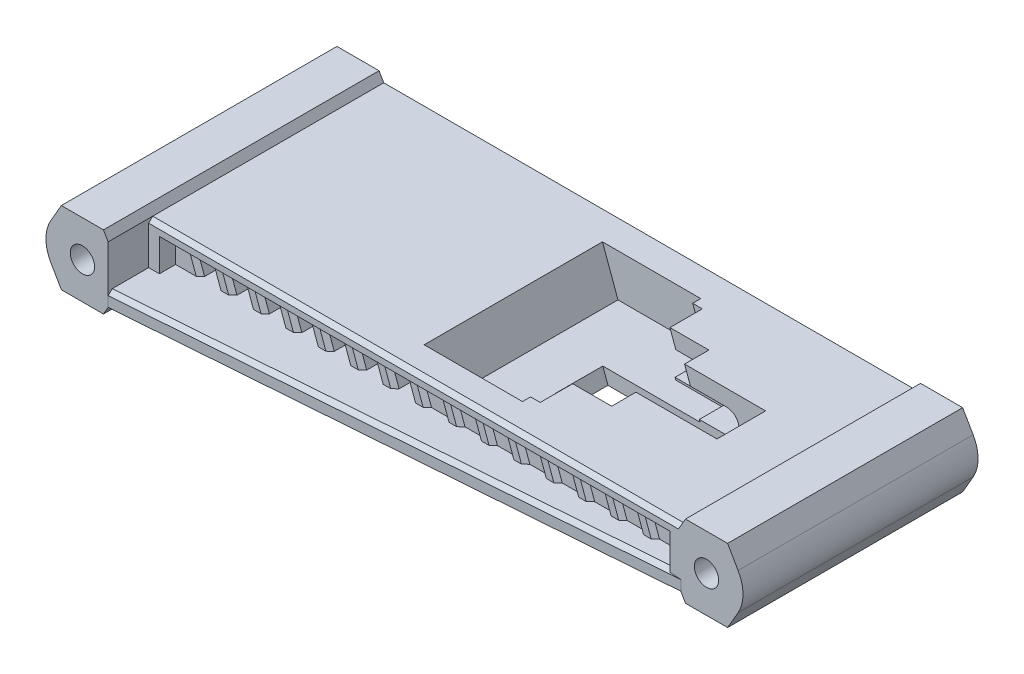
SolidWorks part; units mm, degrees
ref_plane "Front Plane" through (0, 0, 0) normal (0, 0, 1) x (1, 0, 0)
ref_plane "Top Plane" through (0, 0, 0) normal (0, 1, 0) x (1, 0, 0)
ref_plane "Right Plane" through (0, 0, 0) normal (1, 0, 0) x (0, 0, -1)
sketch "Sketch1" plane through (0, 0, 0) normal (0, 0, 1) x (1, 0, 0)
  line L0 (-36, 0) -> (36, 0) construction
  line L1 (0, -10.8775) -> (0, 10.3925) construction
  line L2 (-30.8038, 0) -> (-33.4019, 4.5)
  line L3 (-33.4019, 4.5) -> (-38.5981, 4.5)
  line L4 (-38.5981, 4.5) -> (-41.1962, 0)
  line L5 (-41.1962, 0) -> (-38.5981, -4.5)
  line L6 (-38.5981, -4.5) -> (-33.4019, -4.5)
  line L7 (-33.4019, -4.5) -> (-30.8038, 0)
  line L8 (-32.8246, 3.5) -> (32.8246, 3.5)
  line L9 (32.8246, -3.5) -> (-32.8246, -3.5)
  line L10 (31.5, 1.75) -> (-31.5, 1.75)
  line L11 (-31.5, 1.75) -> (-31.5, -1.75)
  line L12 (-31.5, -1.75) -> (31.5, -1.75)
  line L13 (31.5, 1.75) -> (31.5, -1.75)
  line L14 (33.4019, -4.5) -> (30.8038, 0)
  line L15 (38.5981, -4.5) -> (33.4019, -4.5)
  line L16 (41.1962, 0) -> (38.5981, -4.5)
  line L17 (38.5981, 4.5) -> (41.1962, 0)
  line L18 (33.4019, 4.5) -> (38.5981, 4.5)
  line L19 (30.8038, 0) -> (33.4019, 4.5)
  line L20 (-1.7011, 1.75) -> (-0.4272, -1.75)
  line L21 (0.4272, 1.75) -> (1.7011, -1.75)
  line L22 (-2.4136, 6.6312) -> (2.4136, -6.6312) construction
  line L23 (2.4272, 1.75) -> (3.7011, -1.75)
  line L24 (4.4272, 1.75) -> (5.7011, -1.75)
  line L25 (6.4272, 1.75) -> (7.7011, -1.75)
  line L26 (8.4272, 1.75) -> (9.7011, -1.75)
  line L27 (10.4272, 1.75) -> (11.7011, -1.75)
  line L28 (12.4272, 1.75) -> (13.7011, -1.75)
  line L29 (14.4272, 1.75) -> (15.7011, -1.75)
  line L30 (16.4272, 1.75) -> (17.7011, -1.75)
  line L31 (18.4272, 1.75) -> (19.7011, -1.75)
  line L32 (20.4272, 1.75) -> (21.7011, -1.75)
  line L33 (22.4272, 1.75) -> (23.7011, -1.75)
  line L34 (24.4272, 1.75) -> (25.7011, -1.75)
  line L35 (26.4272, 1.75) -> (27.7011, -1.75)
  line L36 (28.4272, 1.75) -> (29.7011, -1.75)
  line L38 (-3.7011, 1.75) -> (-2.4272, -1.75)
  line L39 (-5.7011, 1.75) -> (-4.4272, -1.75)
  line L40 (-7.7011, 1.75) -> (-6.4272, -1.75)
  line L41 (-9.7011, 1.75) -> (-8.4272, -1.75)
  line L42 (-11.7011, 1.75) -> (-10.4272, -1.75)
  line L43 (-13.7011, 1.75) -> (-12.4272, -1.75)
  line L44 (-15.7011, 1.75) -> (-14.4272, -1.75)
  line L45 (-17.7011, 1.75) -> (-16.4272, -1.75)
  line L46 (-19.7011, 1.75) -> (-18.4272, -1.75)
  line L47 (-21.7011, 1.75) -> (-20.4272, -1.75)
  line L48 (-23.7011, 1.75) -> (-22.4272, -1.75)
  line L49 (-25.7011, 1.75) -> (-24.4272, -1.75)
  line L50 (-27.7011, 1.75) -> (-26.4272, -1.75)
  line L51 (-29.7011, 1.75) -> (-28.4272, -1.75)
  line L53 (21, -7.3355) -> (21, 7.9237) construction
  line L54 (12.07, 0.513) -> (11.6198, 1.75)
  line L55 (-31.7011, 1.75) -> (-30.4272, -1.75)
  line L56 (30.4272, 1.75) -> (31.7011, -1.75)
  line L57 (10.6604, 1.5) -> (21, 1.5)
  line L58 (21, -1.5) -> (10.6604, -1.5)
  circle A0 centre (-36, 0) radius 1.5
  circle A1 centre (-36, 0) radius 4.5 construction
  circle A2 centre (36, 0) radius 4.5 construction
  circle A3 centre (36, 0) radius 1.5
  circle A4 centre (21, 0) radius 1.5
  circle A5 centre (10.6604, 0) radius 1.5
  point P24 (0, -1.75)
  point P25 (0, 1.75)
  point P26 (0, -3.5)
  point P27 (0, 3.5)
  point P68 (21, 0)
  dimension "D1" = 9
  dimension "D2" = 3
  dimension "D11" = 3
  dimension "D3" = 36
  dimension "D4" = 3.5
  dimension "D5" = 1.75
  dimension "D6" = 70
  dimension "D7" = 1
  dimension "D10" = 15
  dimension "D12" = 1.8794
  dimension "D13" = 1.8794
  dimension "D8" = 16
  dimension "D9" = 16
sketch "Sketch2" plane through (0, 0, 0) normal (0, 0, 1) x (1, 0, 0)
  line L0 (32.8246, -3.5) -> (-32.8246, -3.5) construction
  line L3 (-32.8246, 3.5) -> (32.8246, 3.5) construction
  line L4 (-27.7011, 1.75) -> (-26.4272, -1.75) construction
  line L5 (-29.7011, 1.75) -> (-28.4272, -1.75) construction
  line L7 (-36, 0) -> (36, 0) construction
  line L8 (-25.7011, 1.75) -> (-24.4272, -1.75) construction
  line L9 (-23.7011, 1.75) -> (-22.4272, -1.75) construction
  line L10 (-21.7011, 1.75) -> (-20.4272, -1.75) construction
  line L11 (-19.7011, 1.75) -> (-18.4272, -1.75) construction
  line L12 (-17.7011, 1.75) -> (-16.4272, -1.75) construction
  line L13 (-15.7011, 1.75) -> (-14.4272, -1.75) construction
  line L14 (-13.7011, 1.75) -> (-12.4272, -1.75) construction
  line L15 (-11.7011, 1.75) -> (-10.4272, -1.75) construction
  line L16 (-9.7011, 1.75) -> (-8.4272, -1.75) construction
  line L17 (-7.7011, 1.75) -> (-6.4272, -1.75) construction
  line L18 (-5.7011, 1.75) -> (-4.4272, -1.75) construction
  line L19 (-3.7011, 1.75) -> (-2.4272, -1.75) construction
  line L20 (-1.7011, 1.75) -> (-0.4272, -1.75) construction
  line L21 (0, -10.8775) -> (0, 10.3925) construction
  line L22 (0.4272, 1.75) -> (1.7011, -1.75) construction
  line L23 (2.4272, 1.75) -> (3.7011, -1.75) construction
  line L24 (4.4272, 1.75) -> (5.7011, -1.75) construction
  line L25 (6.4272, 1.75) -> (7.7011, -1.75) construction
  line L26 (8.4272, 1.75) -> (9.7011, -1.75) construction
  line L27 (10.4272, 1.75) -> (11.7011, -1.75) construction
  line L28 (12.4272, 1.75) -> (13.7011, -1.75) construction
  line L29 (14.4272, 1.75) -> (15.7011, -1.75) construction
  line L30 (16.4272, 1.75) -> (17.7011, -1.75) construction
  line L31 (18.4272, 1.75) -> (19.7011, -1.75) construction
  line L32 (20.4272, 1.75) -> (21.7011, -1.75) construction
  line L33 (22.4272, 1.75) -> (23.7011, -1.75) construction
  line L34 (24.4272, 1.75) -> (25.7011, -1.75) construction
  line L35 (26.4272, 1.75) -> (27.7011, -1.75) construction
  line L36 (28.4272, 1.75) -> (29.7011, -1.75) construction
  line L38 (-33.4019, -4.5) -> (-30.8038, 0) construction
  line L39 (-38.5981, -4.5) -> (-33.4019, -4.5) construction
  line L40 (-41.1962, 0) -> (-38.5981, -4.5) construction
  line L41 (-38.5981, 4.5) -> (-41.1962, 0) construction
  line L42 (-33.4019, 4.5) -> (-38.5981, 4.5) construction
  line L47 (33.4019, -4.5) -> (30.8038, 0) construction
  line L48 (33.4019, 4.5) -> (38.5981, 4.5) construction
  line L49 (38.5981, 4.5) -> (41.1962, 0) construction
  line L50 (41.1962, 0) -> (38.5981, -4.5) construction
  line L51 (38.5981, -4.5) -> (33.4019, -4.5) construction
  line L52 (32.8246, -3.5) -> (-32.8246, -3.5)
  line L55 (-32.8246, 3.5) -> (32.8246, 3.5)
  line L56 (-27.7011, 1.75) -> (-26.4272, -1.75)
  line L57 (-29.7011, 1.75) -> (-28.4272, -1.75)
  line L59 (-36, 0) -> (36, 0) construction
  line L60 (-25.7011, 1.75) -> (-24.4272, -1.75)
  line L61 (-23.7011, 1.75) -> (-22.4272, -1.75)
  line L62 (-21.7011, 1.75) -> (-20.4272, -1.75)
  line L63 (-19.7011, 1.75) -> (-18.4272, -1.75)
  line L64 (-17.7011, 1.75) -> (-16.4272, -1.75)
  line L65 (-15.7011, 1.75) -> (-14.4272, -1.75)
  line L66 (-13.7011, 1.75) -> (-12.4272, -1.75)
  line L67 (-11.7011, 1.75) -> (-10.4272, -1.75)
  line L68 (-9.7011, 1.75) -> (-8.4272, -1.75)
  line L69 (-7.7011, 1.75) -> (-6.4272, -1.75)
  line L70 (-5.7011, 1.75) -> (-4.4272, -1.75)
  line L71 (-3.7011, 1.75) -> (-2.4272, -1.75)
  line L72 (-1.7011, 1.75) -> (-0.4272, -1.75)
  line L73 (0, -10.8775) -> (0, 10.3925) construction
  line L74 (0.4272, 1.75) -> (1.7011, -1.75)
  line L75 (2.4272, 1.75) -> (3.7011, -1.75)
  line L76 (4.4272, 1.75) -> (5.7011, -1.75)
  line L77 (6.4272, 1.75) -> (7.7011, -1.75)
  line L78 (8.4272, 1.75) -> (9.7011, -1.75)
  line L79 (10.4272, 1.75) -> (11.7011, -1.75)
  line L80 (12.4272, 1.75) -> (13.7011, -1.75)
  line L81 (14.4272, 1.75) -> (15.7011, -1.75)
  line L82 (16.4272, 1.75) -> (17.7011, -1.75)
  line L83 (18.4272, 1.75) -> (19.7011, -1.75)
  line L84 (20.4272, 1.75) -> (21.7011, -1.75)
  line L85 (22.4272, 1.75) -> (23.7011, -1.75)
  line L86 (24.4272, 1.75) -> (25.7011, -1.75)
  line L87 (26.4272, 1.75) -> (27.7011, -1.75)
  line L88 (28.4272, 1.75) -> (29.7011, -1.75)
  line L90 (-33.4019, -4.5) -> (-32.8246, -3.5)
  line L91 (-38.5981, -4.5) -> (-33.4019, -4.5)
  line L92 (-39.8971, -2.25) -> (-38.5981, -4.5)
  line L93 (-38.5981, 4.5) -> (-39.8971, 2.25)
  line L94 (-33.4019, 4.5) -> (-38.5981, 4.5)
  line L95 (28.4272, 1.75) -> (26.4272, 1.75)
  line L98 (27.7011, -1.75) -> (29.7011, -1.75)
  line L99 (33.4019, -4.5) -> (32.8246, -3.5)
  line L100 (33.4019, 4.5) -> (38.5981, 4.5)
  line L101 (38.5981, 4.5) -> (39.8971, 2.25)
  line L102 (39.8971, -2.25) -> (38.5981, -4.5)
  line L103 (38.5981, -4.5) -> (33.4019, -4.5)
  line L104 (-32.8246, 3.5) -> (-33.4019, 4.5)
  line L105 (24.4272, 1.75) -> (22.4272, 1.75)
  line L106 (32.8246, 3.5) -> (33.4019, 4.5)
  line L107 (20.4272, 1.75) -> (18.4272, 1.75)
  line L108 (23.7011, -1.75) -> (25.7011, -1.75)
  line L109 (19.7011, -1.75) -> (21.7011, -1.75)
  line L110 (16.4272, 1.75) -> (14.4272, 1.75)
  line L111 (12.4272, 1.75) -> (10.4272, 1.75)
  line L112 (15.7011, -1.75) -> (17.7011, -1.75)
  line L113 (11.7011, -1.75) -> (13.7011, -1.75)
  line L114 (8.4272, 1.75) -> (6.4272, 1.75)
  line L115 (4.4272, 1.75) -> (2.4272, 1.75)
  line L116 (7.7011, -1.75) -> (9.7011, -1.75)
  line L117 (3.7011, -1.75) -> (5.7011, -1.75)
  line L118 (0.4272, 1.75) -> (-1.7011, 1.75)
  line L119 (-3.7011, 1.75) -> (-5.7011, 1.75)
  line L120 (-0.4272, -1.75) -> (1.7011, -1.75)
  line L121 (-4.4272, -1.75) -> (-2.4272, -1.75)
  line L122 (-7.7011, 1.75) -> (-9.7011, 1.75)
  line L123 (-11.7011, 1.75) -> (-13.7011, 1.75)
  line L124 (-8.4272, -1.75) -> (-6.4272, -1.75)
  line L125 (-12.4272, -1.75) -> (-10.4272, -1.75)
  line L126 (-15.7011, 1.75) -> (-17.7011, 1.75)
  line L127 (-19.7011, 1.75) -> (-21.7011, 1.75)
  line L128 (-16.4272, -1.75) -> (-14.4272, -1.75)
  line L129 (-20.4272, -1.75) -> (-18.4272, -1.75)
  line L130 (-23.7011, 1.75) -> (-25.7011, 1.75)
  line L131 (-27.7011, 1.75) -> (-29.7011, 1.75)
  line L132 (-24.4272, -1.75) -> (-22.4272, -1.75)
  line L133 (-28.4272, -1.75) -> (-26.4272, -1.75)
  circle A0 centre (-36, 0) radius 1.5 construction
  circle A1 centre (-36, 0) radius 4.5 construction
  circle A3 centre (-36, 0) radius 1.5
  arc A4 (-39.8971, 2.25) -> (-39.8971, -2.25) centre (-36, 0) ccw
  circle A5 centre (36, 0) radius 1.5 construction
  arc A6 (39.8971, -2.25) -> (39.8971, 2.25) centre (36, 0) ccw
  circle A7 centre (36, 0) radius 1.5
extrude "Boss-Extrude1" add sketch "Sketch2" along normal blind 2.5
sketch "Sketch3" plane through (0, 0, 2.5) normal (0, 0, 1) x (1, 0, 0)
  line L0 (-41.1962, 0) -> (-38.5981, -4.5) construction
  line L1 (-38.5981, -4.5) -> (-33.4019, -4.5) construction
  line L2 (-33.4019, -4.5) -> (-30.8038, 0) construction
  line L3 (-30.8038, 0) -> (-33.4019, 4.5) construction
  line L4 (-33.4019, 4.5) -> (-38.5981, 4.5) construction
  line L5 (-38.5981, 4.5) -> (-41.1962, 0) construction
  line L7 (-31.5, -1.75) -> (31.5, -1.75) construction
  line L9 (-32.8246, 3.5) -> (32.8246, 3.5) construction
  line L10 (32.8246, -3.5) -> (-32.8246, -3.5) construction
  line L11 (33.4019, -4.5) -> (30.8038, 0) construction
  line L12 (38.5981, -4.5) -> (33.4019, -4.5) construction
  line L13 (41.1962, 0) -> (38.5981, -4.5) construction
  line L14 (38.5981, 4.5) -> (41.1962, 0) construction
  line L15 (33.4019, 4.5) -> (38.5981, 4.5) construction
  line L16 (-29.7011, 1.75) -> (-28.4272, -1.75) construction
  line L18 (-36, 0) -> (36, 0) construction
  line L19 (0, -10.8775) -> (0, 10.3925) construction
  line L20 (-39.8971, -2.25) -> (-38.5981, -4.5)
  line L21 (-38.5981, -4.5) -> (-33.4019, -4.5)
  line L22 (-33.4019, -4.5) -> (-32.8246, -3.5)
  line L23 (-32.8246, 3.5) -> (-33.4019, 4.5)
  line L24 (-33.4019, 4.5) -> (-38.5981, 4.5)
  line L25 (-38.5981, 4.5) -> (-39.8971, 2.25)
  line L26 (-27.7011, 1.75) -> (-29.7011, 1.75)
  line L27 (-28.4272, -1.75) -> (-26.4272, -1.75)
  line L29 (-32.8246, 3.5) -> (32.8246, 3.5)
  line L30 (32.8246, -3.5) -> (-32.8246, -3.5)
  line L31 (33.4019, -4.5) -> (32.8246, -3.5)
  line L32 (38.5981, -4.5) -> (33.4019, -4.5)
  line L33 (39.8971, -2.25) -> (38.5981, -4.5)
  line L34 (38.5981, 4.5) -> (39.8971, 2.25)
  line L35 (33.4019, 4.5) -> (38.5981, 4.5)
  line L36 (-27.7011, 1.75) -> (-26.4272, -1.75) construction
  line L38 (-36, 0) -> (36, 0) construction
  line L39 (0, -10.8775) -> (0, 10.3925) construction
  line L40 (-25.7011, 1.75) -> (-24.4272, -1.75) construction
  line L41 (32.8246, 3.5) -> (33.4019, 4.5)
  line L42 (-23.7011, 1.75) -> (-22.4272, -1.75) construction
  line L43 (-21.7011, 1.75) -> (-20.4272, -1.75) construction
  line L44 (-19.7011, 1.75) -> (-18.4272, -1.75) construction
  line L45 (-17.7011, 1.75) -> (-16.4272, -1.75) construction
  line L46 (-15.7011, 1.75) -> (-14.4272, -1.75) construction
  line L47 (-13.7011, 1.75) -> (-12.4272, -1.75) construction
  line L48 (-11.7011, 1.75) -> (-10.4272, -1.75) construction
  line L49 (-9.7011, 1.75) -> (-8.4272, -1.75) construction
  line L50 (-7.7011, 1.75) -> (-6.4272, -1.75) construction
  line L51 (-5.7011, 1.75) -> (-4.4272, -1.75) construction
  line L52 (-3.7011, 1.75) -> (-2.4272, -1.75) construction
  line L55 (-29.7011, 1.75) -> (-28.4272, -1.75)
  line L56 (-27.7011, 1.75) -> (-26.4272, -1.75)
  line L57 (-25.7011, 1.75) -> (-24.4272, -1.75)
  line L58 (-23.7011, 1.75) -> (-22.4272, -1.75)
  line L59 (-21.7011, 1.75) -> (-20.4272, -1.75)
  line L60 (-19.7011, 1.75) -> (-18.4272, -1.75)
  line L61 (-17.7011, 1.75) -> (-16.4272, -1.75)
  line L62 (-15.7011, 1.75) -> (-14.4272, -1.75)
  line L63 (-13.7011, 1.75) -> (-12.4272, -1.75)
  line L64 (-11.7011, 1.75) -> (-10.4272, -1.75)
  line L65 (-9.7011, 1.75) -> (-8.4272, -1.75)
  line L66 (-7.7011, 1.75) -> (-6.4272, -1.75)
  line L67 (-5.7011, 1.75) -> (-4.4272, -1.75)
  line L68 (-3.7011, 1.75) -> (-2.4272, -1.75)
  line L71 (-24.4272, -1.75) -> (-22.4272, -1.75)
  line L72 (-20.4272, -1.75) -> (-18.4272, -1.75)
  line L73 (-23.7011, 1.75) -> (-25.7011, 1.75)
  line L74 (-19.7011, 1.75) -> (-21.7011, 1.75)
  line L75 (-16.4272, -1.75) -> (-14.4272, -1.75)
  line L76 (-12.4272, -1.75) -> (-10.4272, -1.75)
  line L77 (-15.7011, 1.75) -> (-17.7011, 1.75)
  line L78 (-11.7011, 1.75) -> (-13.7011, 1.75)
  line L79 (-8.4272, -1.75) -> (-6.4272, -1.75)
  line L80 (-7.7011, 1.75) -> (-9.7011, 1.75)
  line L81 (-4.4272, -1.75) -> (-2.4272, -1.75)
  line L83 (-3.7011, 1.75) -> (-5.7011, 1.75)
  circle A0 centre (-36, 0) radius 4.5 construction
  circle A1 centre (-36, 0) radius 1.5 construction
  circle A3 centre (36, 0) radius 1.5 construction
  arc A4 (-39.8971, 2.25) -> (-39.8971, -2.25) centre (-36, 0) ccw
  circle A5 centre (-36, 0) radius 1.5
  circle A7 centre (36, 0) radius 1.5
  arc A8 (39.8971, -2.25) -> (39.8971, 2.25) centre (36, 0) ccw
extrude "Boss-Extrude2" add sketch "Sketch3" along normal blind 24
sketch "Sketch6" plane through (0, 0, 26.5) normal (0, 0, 1) x (1, 0, 0)
  line L0 (-38.5981, 4.5) -> (-41.1962, 0) construction
  line L1 (-33.4019, 4.5) -> (-38.5981, 4.5) construction
  line L2 (-30.8038, 0) -> (-33.4019, 4.5) construction
  line L3 (-32.8246, 3.5) -> (32.8246, 3.5) construction
  line L4 (30.8038, 0) -> (33.4019, 4.5) construction
  line L5 (33.4019, 4.5) -> (38.5981, 4.5) construction
  line L6 (38.5981, 4.5) -> (41.1962, 0) construction
  line L7 (41.1962, 0) -> (38.5981, -4.5) construction
  line L8 (38.5981, -4.5) -> (33.4019, -4.5) construction
  line L9 (33.4019, -4.5) -> (30.8038, 0) construction
  line L10 (32.8246, -3.5) -> (-32.8246, -3.5) construction
  line L11 (-33.4019, -4.5) -> (-30.8038, 0) construction
  line L12 (-38.5981, -4.5) -> (-33.4019, -4.5) construction
  line L13 (-41.1962, 0) -> (-38.5981, -4.5) construction
  line L14 (-31.5, -1.75) -> (31.5, -1.75) construction
  line L15 (31.5, 1.75) -> (-31.5, 1.75) construction
  line L16 (-29.7011, 1.75) -> (-28.4272, -1.75) construction
  line L17 (-27.7011, 1.75) -> (-26.4272, -1.75) construction
  line L18 (-25.7011, 1.75) -> (-24.4272, -1.75) construction
  line L19 (-23.7011, 1.75) -> (-22.4272, -1.75) construction
  line L20 (-21.7011, 1.75) -> (-20.4272, -1.75) construction
  line L21 (-19.7011, 1.75) -> (-18.4272, -1.75) construction
  line L22 (-17.7011, 1.75) -> (-16.4272, -1.75) construction
  line L23 (-15.7011, 1.75) -> (-14.4272, -1.75) construction
  line L24 (-13.7011, 1.75) -> (-12.4272, -1.75) construction
  line L25 (-11.7011, 1.75) -> (-10.4272, -1.75) construction
  line L26 (-9.7011, 1.75) -> (-8.4272, -1.75) construction
  line L27 (-7.7011, 1.75) -> (-6.4272, -1.75) construction
  line L28 (-5.7011, 1.75) -> (-4.4272, -1.75) construction
  line L29 (-3.7011, 1.75) -> (-2.4272, -1.75) construction
  line L30 (-1.7011, 1.75) -> (-0.4272, -1.75) construction
  line L31 (0.4272, 1.75) -> (1.7011, -1.75) construction
  line L32 (2.4272, 1.75) -> (3.7011, -1.75) construction
  line L33 (4.4272, 1.75) -> (5.7011, -1.75) construction
  line L34 (6.4272, 1.75) -> (7.7011, -1.75) construction
  line L35 (8.4272, 1.75) -> (9.7011, -1.75) construction
  line L36 (10.4272, 1.75) -> (11.7011, -1.75) construction
  line L37 (12.4272, 1.75) -> (13.7011, -1.75) construction
  line L38 (14.4272, 1.75) -> (15.7011, -1.75) construction
  line L39 (16.4272, 1.75) -> (17.7011, -1.75) construction
  line L40 (18.4272, 1.75) -> (19.7011, -1.75) construction
  line L41 (20.4272, 1.75) -> (21.7011, -1.75) construction
  line L42 (22.4272, 1.75) -> (23.7011, -1.75) construction
  line L43 (24.4272, 1.75) -> (25.7011, -1.75) construction
  line L44 (26.4272, 1.75) -> (27.7011, -1.75) construction
  line L45 (28.4272, 1.75) -> (29.7011, -1.75) construction
  line L46 (-38.5981, 4.5) -> (-39.8971, 2.25)
  line L47 (-33.4019, 4.5) -> (-38.5981, 4.5)
  line L48 (-32.8246, 3.5) -> (-33.4019, 4.5)
  line L49 (-32.8246, 3.5) -> (32.8246, 3.5)
  line L50 (32.8246, 3.5) -> (33.4019, 4.5)
  line L51 (33.4019, 4.5) -> (38.5981, 4.5)
  line L52 (38.5981, 4.5) -> (39.8971, 2.25)
  line L53 (39.8971, -2.25) -> (38.5981, -4.5)
  line L54 (38.5981, -4.5) -> (33.4019, -4.5)
  line L55 (33.4019, -4.5) -> (32.8246, -3.5)
  line L56 (32.8246, -3.5) -> (-32.8246, -3.5)
  line L57 (-33.4019, -4.5) -> (-32.8246, -3.5)
  line L58 (-38.5981, -4.5) -> (-33.4019, -4.5)
  line L59 (-39.8971, -2.25) -> (-38.5981, -4.5)
  line L60 (-28.4272, -1.75) -> (-26.4272, -1.75)
  line L61 (28.4272, 1.75) -> (26.4272, 1.75)
  line L62 (-29.7011, 1.75) -> (-28.4272, -1.75)
  line L63 (-27.7011, 1.75) -> (-26.4272, -1.75)
  line L64 (-25.7011, 1.75) -> (-24.4272, -1.75)
  line L65 (-23.7011, 1.75) -> (-22.4272, -1.75)
  line L66 (-21.7011, 1.75) -> (-20.4272, -1.75)
  line L67 (-19.7011, 1.75) -> (-18.4272, -1.75)
  line L68 (-17.7011, 1.75) -> (-16.4272, -1.75)
  line L69 (-15.7011, 1.75) -> (-14.4272, -1.75)
  line L70 (-13.7011, 1.75) -> (-12.4272, -1.75)
  line L71 (-11.7011, 1.75) -> (-10.4272, -1.75)
  line L72 (-9.7011, 1.75) -> (-8.4272, -1.75)
  line L73 (-7.7011, 1.75) -> (-6.4272, -1.75)
  line L74 (-5.7011, 1.75) -> (-4.4272, -1.75)
  line L75 (-3.7011, 1.75) -> (-2.4272, -1.75)
  line L76 (-1.7011, 1.75) -> (-0.4272, -1.75)
  line L77 (0.4272, 1.75) -> (1.7011, -1.75)
  line L78 (2.4272, 1.75) -> (3.7011, -1.75)
  line L79 (4.4272, 1.75) -> (5.7011, -1.75)
  line L80 (6.4272, 1.75) -> (7.7011, -1.75)
  line L81 (8.4272, 1.75) -> (9.7011, -1.75)
  line L82 (10.4272, 1.75) -> (11.7011, -1.75)
  line L83 (12.4272, 1.75) -> (13.7011, -1.75)
  line L84 (14.4272, 1.75) -> (15.7011, -1.75)
  line L85 (16.4272, 1.75) -> (17.7011, -1.75)
  line L86 (18.4272, 1.75) -> (19.7011, -1.75)
  line L87 (20.4272, 1.75) -> (21.7011, -1.75)
  line L88 (22.4272, 1.75) -> (23.7011, -1.75)
  line L89 (24.4272, 1.75) -> (25.7011, -1.75)
  line L90 (26.4272, 1.75) -> (27.7011, -1.75)
  line L91 (28.4272, 1.75) -> (29.7011, -1.75)
  line L92 (-24.4272, -1.75) -> (-22.4272, -1.75)
  line L93 (-20.4272, -1.75) -> (-18.4272, -1.75)
  line L94 (-16.4272, -1.75) -> (-14.4272, -1.75)
  line L95 (-12.4272, -1.75) -> (-10.4272, -1.75)
  line L96 (-8.4272, -1.75) -> (-6.4272, -1.75)
  line L97 (-4.4272, -1.75) -> (-2.4272, -1.75)
  line L98 (-0.4272, -1.75) -> (1.7011, -1.75)
  line L99 (3.7011, -1.75) -> (5.7011, -1.75)
  line L100 (7.7011, -1.75) -> (9.7011, -1.75)
  line L101 (11.7011, -1.75) -> (13.7011, -1.75)
  line L102 (15.7011, -1.75) -> (17.7011, -1.75)
  line L103 (19.7011, -1.75) -> (21.7011, -1.75)
  line L104 (23.7011, -1.75) -> (25.7011, -1.75)
  line L105 (27.7011, -1.75) -> (29.7011, -1.75)
  line L106 (-27.7011, 1.75) -> (-29.7011, 1.75)
  line L107 (-23.7011, 1.75) -> (-25.7011, 1.75)
  line L108 (-19.7011, 1.75) -> (-21.7011, 1.75)
  line L109 (-15.7011, 1.75) -> (-17.7011, 1.75)
  line L110 (-11.7011, 1.75) -> (-13.7011, 1.75)
  line L111 (-7.7011, 1.75) -> (-9.7011, 1.75)
  line L112 (-3.7011, 1.75) -> (-5.7011, 1.75)
  line L113 (0.4272, 1.75) -> (-1.7011, 1.75)
  line L114 (4.4272, 1.75) -> (2.4272, 1.75)
  line L115 (8.4272, 1.75) -> (6.4272, 1.75)
  line L116 (12.4272, 1.75) -> (10.4272, 1.75)
  line L117 (16.4272, 1.75) -> (14.4272, 1.75)
  line L118 (20.4272, 1.75) -> (18.4272, 1.75)
  line L119 (24.4272, 1.75) -> (22.4272, 1.75)
  circle A0 centre (-36, 0) radius 4.5 construction
  circle A1 centre (-36, 0) radius 1.5 construction
  circle A2 centre (36, 0) radius 1.5 construction
  circle A3 centre (36, 0) radius 4.5 construction
  arc A4 (-39.8971, 2.25) -> (-39.8971, -2.25) centre (-36, 0) ccw
  circle A5 centre (-36, 0) radius 1.5
  circle A6 centre (36, 0) radius 1.5
  arc A7 (39.8971, -2.25) -> (39.8971, 2.25) centre (36, 0) ccw
extrude "Boss-Extrude3" add sketch "Sketch6" along normal blind 0.5
sketch "Sketch7" plane through (0, 0, 27) normal (0, 0, 1) x (1, 0, 0)
  line L0 (-33.4019, 4.5) -> (-38.5981, 4.5) construction
  line L1 (-38.5981, 4.5) -> (-41.1962, 0) construction
  line L2 (-41.1962, 0) -> (-38.5981, -4.5) construction
  line L3 (-38.5981, -4.5) -> (-33.4019, -4.5) construction
  line L4 (-33.4019, -4.5) -> (-30.8038, 0) construction
  line L5 (32.8246, -3.5) -> (-32.8246, -3.5) construction
  line L7 (-32.8246, 3.5) -> (32.8246, 3.5) construction
  line L8 (31.5, 1.75) -> (-31.5, 1.75) construction
  line L9 (-31.5, -1.75) -> (31.5, -1.75) construction
  line L10 (-31.5, 1.75) -> (-31.5, -1.75) construction
  line L11 (31.5, 1.75) -> (31.5, -1.75) construction
  line L12 (30.8038, 0) -> (33.4019, 4.5) construction
  line L13 (33.4019, 4.5) -> (38.5981, 4.5) construction
  line L14 (38.5981, 4.5) -> (41.1962, 0) construction
  line L15 (41.1962, 0) -> (38.5981, -4.5) construction
  line L16 (38.5981, -4.5) -> (33.4019, -4.5) construction
  line L17 (33.4019, -4.5) -> (30.8038, 0) construction
  line L18 (-33.4019, 4.5) -> (-38.5981, 4.5)
  line L19 (-38.5981, 4.5) -> (-39.8971, 2.25)
  line L20 (-39.8971, -2.25) -> (-38.5981, -4.5)
  line L21 (-38.5981, -4.5) -> (-33.4019, -4.5)
  line L22 (-33.4019, -4.5) -> (-32.8246, -3.5)
  line L23 (32.8246, -3.5) -> (-32.8246, -3.5)
  line L25 (-32.8246, 3.5) -> (32.8246, 3.5)
  line L26 (31.5, 1.75) -> (-31.5, 1.75)
  line L27 (-31.5, -1.75) -> (31.5, -1.75)
  line L28 (-31.5, 1.75) -> (-31.5, -1.75)
  line L29 (31.5, 1.75) -> (31.5, -1.75)
  line L30 (32.8246, 3.5) -> (33.4019, 4.5)
  line L31 (33.4019, 4.5) -> (38.5981, 4.5)
  line L32 (38.5981, 4.5) -> (39.8971, 2.25)
  line L33 (39.8971, -2.25) -> (38.5981, -4.5)
  line L34 (38.5981, -4.5) -> (33.4019, -4.5)
  line L35 (33.4019, -4.5) -> (32.8246, -3.5)
  line L36 (-32.8246, 3.5) -> (-33.4019, 4.5)
  circle A0 centre (-36, 0) radius 1.5 construction
  circle A1 centre (-36, 0) radius 1.5
  circle A2 centre (-36, 0) radius 4.5 construction
  circle A3 centre (36, 0) radius 4.5 construction
  arc A4 (-39.8971, 2.25) -> (-39.8971, -2.25) centre (-36, 0) ccw
  arc A5 (39.8971, -2.25) -> (39.8971, 2.25) centre (36, 0) ccw
  circle A6 centre (36, 0) radius 1.5 construction
  circle A7 centre (36, 0) radius 1.5
extrude "Boss-Extrude4" add sketch "Sketch7" along normal blind 7
sketch "Sketch8" plane through (0, 0, 0) normal (0, 1, 0) x (1, 0, 0)
  line L0 (40.5, -34) -> (-32.8246, -34)
  line L1 (-32.8246, -34) -> (32.8246, -29)
  line L2 (32.8246, -34) -> (32.8246, 0) construction
  line L3 (32.8246, -29) -> (40.5, -29)
  line L4 (40.5, -34) -> (40.5, 0) construction
  line L5 (40.5, -29) -> (40.5, -34)
  dimension "D1" = 5
extrude "Cut-Extrude1" cut sketch "Sketch8" against normal mid plane 10
sketch "Sketch9" plane through (0, 3.5, 0) normal (0, 1, 0) x (1, 0, 0)
  line L0 (32.8246, -29) -> (-32.8246, -29)
  line L1 (-32.8246, -34) -> (-32.8246, 0) construction
  line L2 (-32.8246, -29) -> (-32.8246, -34)
  line L3 (-32.8246, -34) -> (32.8246, -29)
extrude "Cut-Extrude2" cut sketch "Sketch9" against normal blind 5.25
chamfer "Chamfer1" distance 0.5 angle 45 33 edges at (17.0642, 0, 27) (19.0642, 0, 27) (21.0642, 0, 27) (23.0642, 0, 27) (25.0642, 0, 27) (27.0642, 0, 27) (29.0642, 0, 27) (15.0642, 0, 27) (13.0642, 0, 27) (11.0642, 0, 27) (9.0642, 0, 27) (7.0642, 0, 27) (5.0642, 0, 27) (3.0642, 0, 27) (1.0642, 0, 27) (-1.0642, 0, 27) (-3.0642, 0, 27) (-5.0642, 0, 27) (-7.0642, 0, 27) (-9.0642, 0, 27) (-11.0642, 0, 27) (-13.0642, 0, 27) (-15.0642, 0, 27) (-17.0642, 0, 27) (-19.0642, 0, 27) (-21.0642, 0, 27) (-23.0642, 0, 27) (-25.0642, 0, 27) (-27.0642, 0, 27) (-29.0642, 0, 27) (0, -1.75, 31.5) (0, 1.75, 29) (0, 3.5, 29)
ref_plane "Plane1" through (0, 0, 14.5) normal (0, 0, 1) x (1, 0, 0)
sketch "Sketch10" plane through (0, 0, 14.5) normal (0, 0, 1) x (1, 0, 0)
  line L4 (-32.8246, 3.5) -> (32.8246, 3.5) construction
  line L6 (26.4272, 1.75) -> (27.7011, -1.75) construction
  line L8 (32.8246, -3.5) -> (-32.8246, -3.5) construction
  line L14 (0.4272, 1.75) -> (1.7011, -1.75) construction
  line L15 (-0.2097, 3.5) -> (25.7903, 3.5)
  line L17 (26.4272, 1.75) -> (27.7011, -1.75)
  line L18 (28.3381, -3.5) -> (6.3381, -3.5)
  line L19 (-31.5, -1.75) -> (31.5, -1.75) construction
  line L20 (1.7011, -1.75) -> (5.7011, -1.75)
  line L21 (0.4272, 1.75) -> (1.7011, -1.75)
  line L22 (0.4272, 1.75) -> (-0.2097, 3.5)
  line L23 (5.7011, -1.75) -> (6.3381, -3.5)
  line L24 (27.7011, -1.75) -> (28.3381, -3.5)
  line L25 (26.4272, 1.75) -> (25.7903, 3.5)
extrude "Cut-Extrude3" cut sketch "Sketch10" against normal mid plane 6
sketch "Sketch11" plane through (0, 0, 14.5) normal (0, 0, 1) x (1, 0, 0)
  line L0 (0.4272, 1.75) -> (1.7011, -1.75) construction
  line L4 (0.4272, 1.75) -> (1.7011, -1.75)
  line L5 (16.4272, 1.75) -> (17.7011, -1.75) construction
  line L6 (-31.5, -1.75) -> (31.5, -1.75) construction
  line L7 (-32.8246, 3.5) -> (32.8246, 3.5) construction
  line L8 (0.4272, 1.75) -> (-0.2097, 3.5)
  line L9 (16.4272, 1.75) -> (17.7011, -1.75)
  line L10 (1.7011, -1.75) -> (17.7011, -1.75)
  line L11 (-0.2097, 3.5) -> (15.7903, 3.5)
  line L12 (16.4272, 1.75) -> (15.7903, 3.5)
extrude "Cut-Extrude4" cut sketch "Sketch11" against normal mid plane 12
sketch "Sketch12" plane through (0, 0, 14.5) normal (0, 0, 1) x (1, 0, 0)
  line L3 (10.4272, 1.75) -> (11.7011, -1.75) construction
  line L4 (-32.8246, 3.5) -> (32.8246, 3.5) construction
  line L5 (-31.5, -1.75) -> (31.5, -1.75) construction
  line L6 (-2.3381, 3.5) -> (9.7903, 3.5)
  line L7 (10.4272, 1.75) -> (11.7011, -1.75)
  line L8 (-1.7011, 1.75) -> (-2.3381, 3.5)
  line L9 (10.4272, 1.75) -> (9.7903, 3.5)
  line L10 (-1.7011, 1.75) -> (-0.4272, -1.75) construction
  line L11 (-0.4272, -1.75) -> (11.7011, -1.75)
  line L12 (-1.7011, 1.75) -> (-0.4272, -1.75)
extrude "Cut-Extrude5" cut sketch "Sketch12" against normal mid plane 22
sketch "Sketch13" plane through (0, 0, 14.5) normal (0, 0, 1) x (1, 0, 0)
  line L0 (8.4272, 1.75) -> (9.7011, -1.75) construction
  line L1 (12.07, 0.513) -> (11.6198, 1.75) construction
  line L2 (10.6604, 1.5) -> (21, 1.5) construction
  line L3 (21, -1.5) -> (10.6604, -1.5) construction
  line L4 (8.4272, 1.75) -> (9.2509, -0.513)
  line L5 (11.7108, 1.5) -> (11.6198, 1.75)
  line L6 (11.7108, 1.5) -> (21, 1.5)
  line L7 (21, -1.5) -> (10.6604, -1.5)
  line L8 (8.4272, 1.75) -> (7.7903, 3.5)
  line L9 (11.6198, 1.75) -> (10.9828, 3.5)
  line L10 (-32.8246, 3.5) -> (32.8246, 3.5) construction
  line L11 (7.7903, 3.5) -> (10.9828, 3.5)
  circle A0 centre (10.6604, 0) radius 1.5 construction
  circle A1 centre (21, 0) radius 1.5 construction
  arc A2 (9.2509, -0.513) -> (10.6604, -1.5) centre (10.6604, 0) ccw
  arc A3 (21, -1.5) -> (21, 1.5) centre (21, 0) ccw
extrude "Cut-Extrude6" cut sketch "Sketch13" against normal mid plane 20
